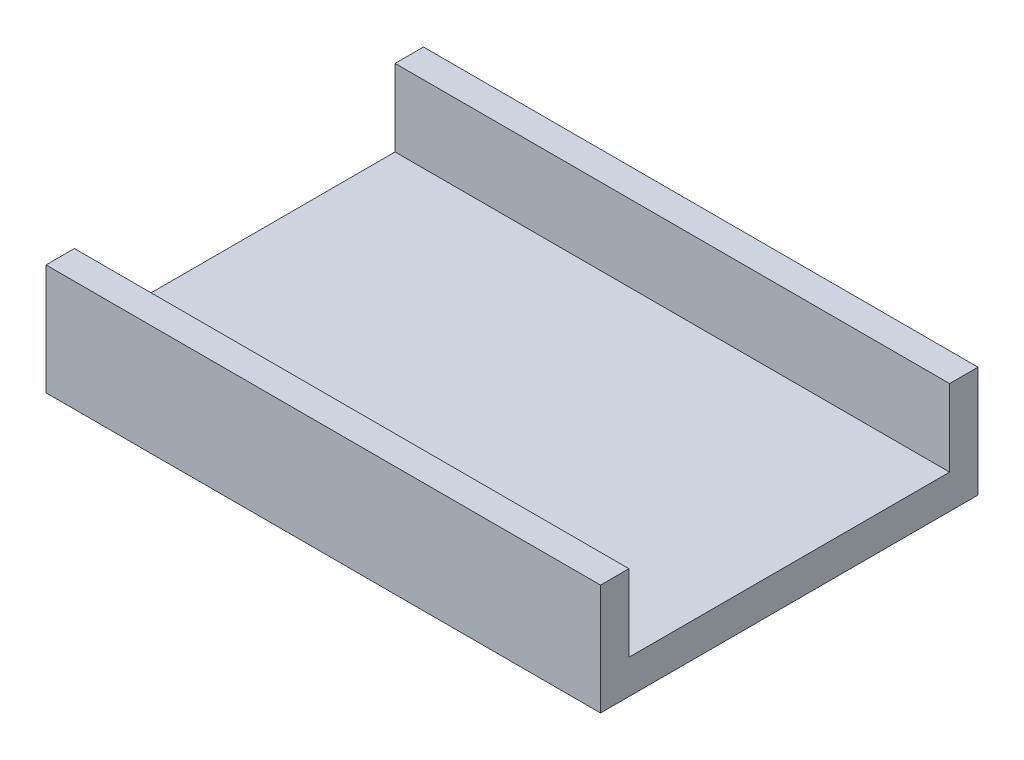
SolidWorks part; units mm, degrees
material "ABS"
ref_plane "Front Plane" through (0, 0, 0) normal (0, 0, 1) x (1, 0, 0)
ref_plane "Top Plane" through (0, 0, 0) normal (0, 1, 0) x (1, 0, 0)
ref_plane "Right Plane" through (0, 0, 0) normal (1, 0, 0) x (0, 0, -1)
sketch "Sketch1" plane through (0, 0, 0) normal (0, 1, 0) x (1, 0, 0)
  line L1 (48.8, 33.2187) -> (-48.8, 33.2187)
  line L2 (48.8, 33.2187) -> (48.8, -33.2187)
  line L3 (48.8, -33.2187) -> (-48.8, -33.2187)
  line L4 (-48.8, 33.2187) -> (-48.8, -33.2187)
  line L5 (48.8, 33.2187) -> (-48.8, -33.2187) construction
  line L6 (48.8, -33.2187) -> (-48.8, 33.2187) construction
  point P0 (0, 0)
  dimension "D1" = 97.6
  dimension "D2" = 66.4375
extrude "Boss-Extrude1" add sketch "Sketch1" along normal blind 6
sketch "Sketch3" plane through (0, 6, 0) normal (0, 1, 0) x (1, 0, 0)
  line L0 (48.8, -33.2187) -> (48.8, 33.2187) construction
  line L1 (30.8, 27) -> (-24.2, 27)
  line L2 (30.8, 27) -> (30.8, -27)
  line L3 (30.8, -27) -> (-24.2, -27)
  line L4 (-24.2, 27) -> (-24.2, -27)
  line L5 (30.8, 27) -> (-24.2, -27) construction
  line L6 (30.8, -27) -> (-24.2, 27) construction
  point P0 (3.3, 0)
  dimension "D1" = 54
  dimension "D2" = 55
  dimension "D3" = 0
  dimension "D4" = 18
sketch "Sketch4" plane through (0, 6, 0) normal (0, 1, 0) x (1, 0, 0)
  line L0 (30.8, -27) -> (30.8, -33.2187)
  line L1 (-48.8, -33.2187) -> (48.8, -33.2187) construction
  line L2 (30.8, -33.2187) -> (30.8, 33.2187)
  line L3 (48.8, 33.2187) -> (-48.8, 33.2187) construction
  line L4 (30.8, 33.2187) -> (30.8, 27)
  line L5 (30.8, 27) -> (48.8, 27)
  line L6 (48.8, -33.2187) -> (48.8, 33.2187) construction
  line L7 (48.8, 27) -> (-48.8, 27)
  line L8 (-48.8, 33.2187) -> (-48.8, -33.2187) construction
  line L9 (-48.8, 27) -> (-24.2, 27)
  line L10 (-24.2, 27) -> (-24.2, 33.2187)
  line L11 (-24.2, 33.2187) -> (-24.2, -33.2187)
  line L13 (-24.2, -33.2187) -> (-48.8, -33.2187)
  line L14 (-24.2, -33.2187) -> (-24.2, 33.2187)
  line L15 (-24.2, 33.2187) -> (-48.8, 33.2187)
  line L16 (-48.8, -33.2187) -> (-48.8, 33.2187)
  line L17 (-48.8, 33.2187) -> (48.8, 33.2187)
  line L18 (-48.8, 33.2187) -> (-48.8, 27)
  line L19 (-48.8, 27) -> (48.8, 27)
  line L20 (48.8, 33.2187) -> (48.8, 27)
  line L21 (48.8, 33.2187) -> (30.8, 33.2187)
  line L22 (48.8, 33.2187) -> (48.8, -33.2187)
  line L23 (48.8, -33.2187) -> (30.8, -33.2187)
  line L24 (30.8, 33.2187) -> (30.8, -33.2187)
  line L25 (48.8, -33.2187) -> (-48.8, -33.2187)
  line L26 (48.8, -33.2187) -> (48.8, -27)
  line L27 (48.8, -27) -> (-48.8, -27)
  line L28 (-48.8, -33.2187) -> (-48.8, -27)
  line M1 (-48.8, 33.2187) -> (-48.8, -33.2187)
  line M2 (-48.8, -33.2187) -> (48.8, -33.2187)
  line M3 (48.8, -33.2187) -> (48.8, 33.2187)
  line M4 (48.8, 33.2187) -> (-48.8, 33.2187)
extrude "Boss-Extrude2" add sketch "Sketch4" along normal blind 13.5 contours L27 L11 L7 M1 | L14 L27 L16 M2 | L0 L27 L14 M2 | L27 L0 M3 M2 | L27 L22 L5 L2 | L2 L5 M3 M4 | L7 L10 M4 M1 | L10 L7 L2 M4 region at (39.8, 6, 30.1094) region at (39.8, 6, 0) region at (3.3, 6, 30.1094) region at (3.3, 6, -30.1094) region at (39.8, 6, -30.1094) region at (-36.5, 6, 0) region at (-36.5, 6, 30.1094) region at (-36.5, 6, -30.1094)
sketch "Sketch5" plane through (0, 19.5, 0) normal (0, 1, 0) x (1, 0, 0)
  line L0 (-46.8936, -20) -> (-12.1997, -20)
  line L1 (-46.8936, -20) -> (-46.8936, 10)
  line L2 (-12.1997, -20) -> (-12.1997, 10)
  line L3 (-46.8936, 10) -> (-12.1997, 10)
  line L4 (-46.8936, -20) -> (-12.1997, 10) construction
  line L5 (-12.1997, -20) -> (-46.8936, 10) construction
  point P1 (-29.5467, -5)
  dimension "D1" = 30
  dimension "D2" = 5
extrude "Cut-Extrude1" [suppressed] cut sketch "Sketch5" against normal blind 13.5
sketch "Sketch6" plane through (0, 19.5, 0) normal (0, 1, 0) x (1, 0, 0)
  line L0 (48.8, -33.2187) -> (48.8, 33.2187) construction
  line L1 (48.8, 28.2187) -> (-48.8, 28.2187)
  line L2 (48.8, 28.2187) -> (48.8, -28.2187)
  line L3 (48.8, -28.2187) -> (-48.8, -28.2187)
  line L4 (-48.8, 28.2187) -> (-48.8, -28.2187)
  line L5 (-48.8, 33.2187) -> (-48.8, -33.2187) construction
  line L6 (48.8, 33.2187) -> (-48.8, 33.2187) construction
  line L7 (-48.8, -33.2187) -> (48.8, -33.2187) construction
  dimension "D1" = 5
  dimension "D2" = 5
extrude "Cut-Extrude2" cut sketch "Sketch6" against normal blind 13.5
